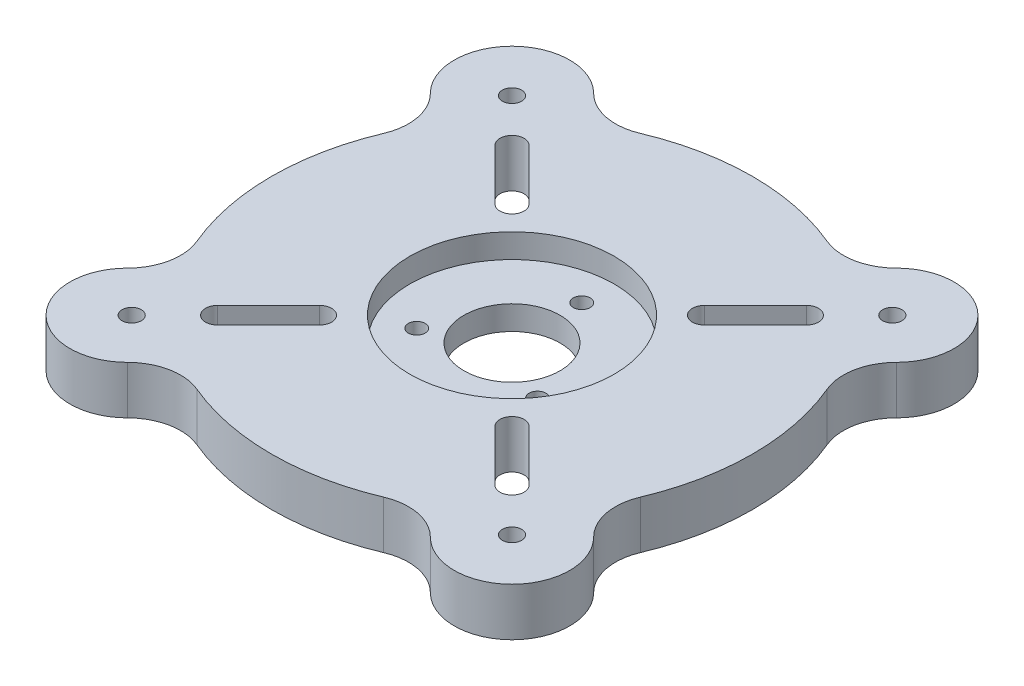
SolidWorks part; units mm, degrees
material "Cast Alloy Steel"
ref_plane "Front Plane" through (0, 0, 0) normal (0, 0, 1) x (1, 0, 0)
ref_plane "Top Plane" through (0, 0, 0) normal (0, 1, 0) x (1, 0, 0)
ref_plane "Right Plane" through (0, 0, 0) normal (1, 0, 0) x (0, 0, -1)
sketch "Sketch1" plane through (0, 0, 0) normal (0, 1, 0) x (1, 0, 0)
  line L0 (-39.9515, -39.9515) -> (39.9515, 39.9515) construction
  line L1 (-48.4368, -31.4663) -> (31.4663, 48.4368) construction
  line L2 (-31.4663, -48.4368) -> (48.4368, 31.4663) construction
  line L3 (0, 0) -> (0, 50) construction
  line L4 (39.9515, -39.9515) -> (-39.9515, 39.9515) construction
  line L5 (48.4368, -31.4663) -> (-31.4663, 48.4368) construction
  line L6 (31.4663, -48.4368) -> (-48.4368, 31.4663) construction
  line L7 (20, 20) -> (30.6066, 30.6066) construction
  line L8 (18.2322, 21.7678) -> (28.8388, 32.3744)
  line L9 (21.7678, 18.2322) -> (32.3744, 28.8388)
  line L10 (20, -20) -> (30.6066, -30.6066) construction
  line L11 (21.7678, -18.2322) -> (32.3744, -28.8388)
  line L12 (18.2322, -21.7678) -> (28.8388, -32.3744)
  line L13 (-20, -20) -> (-30.6066, -30.6066) construction
  line L14 (-18.2322, -21.7678) -> (-28.8388, -32.3744)
  line L15 (-21.7678, -18.2322) -> (-32.3744, -28.8388)
  line L16 (-20, 20) -> (-30.6066, 30.6066) construction
  line L17 (-21.7678, 18.2322) -> (-32.3744, 28.8388)
  line L18 (-18.2322, 21.7678) -> (-28.8388, 32.3744)
  circle A0 centre (0, 0) radius 50
  arc A1 (-48.4368, -31.4663) -> (-31.4663, -48.4368) centre (-39.9515, -39.9515) ccw construction
  arc A2 (48.4368, 31.4663) -> (31.4663, 48.4368) centre (39.9515, 39.9515) ccw construction
  arc A3 (48.4368, -31.4663) -> (31.4663, -48.4368) centre (39.9515, -39.9515) cw construction
  arc A4 (-48.4368, 31.4663) -> (-31.4663, 48.4368) centre (-39.9515, 39.9515) cw construction
  arc A5 (31.4663, 48.4368) -> (19.4135, 46.0773) centre (23.6858, 56.2173) cw
  arc A6 (48.4368, 31.4663) -> (46.0773, 19.4135) centre (56.2173, 23.6858) ccw
  arc A7 (18.2322, 21.7678) -> (21.7678, 18.2322) centre (20, 20) ccw
  arc A8 (32.3744, 28.8388) -> (28.8388, 32.3744) centre (30.6066, 30.6066) ccw
  circle A9 centre (39.5312, 39.5312) radius 2
  arc A10 (31.4663, 48.4368) -> (48.4368, 31.4663) centre (39.9515, 39.9515) cw
  arc A11 (48.4368, -31.4663) -> (31.4663, -48.4368) centre (39.9515, -39.9515) cw
  arc A12 (48.4368, -31.4663) -> (46.0773, -19.4135) centre (56.2173, -23.6858) cw
  arc A13 (31.4663, -48.4368) -> (19.4135, -46.0773) centre (23.6858, -56.2173) ccw
  circle A14 centre (39.5312, -39.5312) radius 2
  circle A15 centre (0, 0) radius 50
  arc A16 (21.7678, -18.2322) -> (18.2322, -21.7678) centre (20, -20) ccw
  arc A17 (28.8388, -32.3744) -> (32.3744, -28.8388) centre (30.6066, -30.6066) ccw
  arc A18 (-31.4663, -48.4368) -> (-48.4368, -31.4663) centre (-39.9515, -39.9515) cw
  arc A19 (-31.4663, -48.4368) -> (-19.4135, -46.0773) centre (-23.6858, -56.2173) cw
  arc A20 (-48.4368, -31.4663) -> (-46.0773, -19.4135) centre (-56.2173, -23.6858) ccw
  circle A21 centre (-39.5312, -39.5312) radius 2
  circle A22 centre (0, 0) radius 50
  arc A23 (-18.2322, -21.7678) -> (-21.7678, -18.2322) centre (-20, -20) ccw
  arc A24 (-32.3744, -28.8388) -> (-28.8388, -32.3744) centre (-30.6066, -30.6066) ccw
  arc A25 (-48.4368, 31.4663) -> (-31.4663, 48.4368) centre (-39.9515, 39.9515) cw
  arc A26 (-48.4368, 31.4663) -> (-46.0773, 19.4135) centre (-56.2173, 23.6858) cw
  arc A27 (-31.4663, 48.4368) -> (-19.4135, 46.0773) centre (-23.6858, 56.2173) ccw
  circle A28 centre (-39.5312, 39.5312) radius 2
  circle A29 centre (0, 0) radius 50
  arc A30 (-21.7678, 18.2322) -> (-18.2322, 21.7678) centre (-20, 20) ccw
  arc A31 (-28.8388, 32.3744) -> (-32.3744, 28.8388) centre (-30.6066, 30.6066) ccw
  point P5 (0, 0)
  point P13 (0, 0)
  point P24 (25.3033, 25.3033)
  point P45 (25.3033, -25.3033)
  point P63 (-25.3033, -25.3033)
  point P81 (-25.3033, 25.3033)
  point P90 (0, 0)
  dimension "D1" = 100
  dimension "D2" = 12
  dimension "D5" = 2.5
  dimension "D8" = 4
  dimension "D10" = 39.5312
  dimension "D3" = 113
  dimension "D4" = 45
  dimension "D6" = 15
  dimension "D7" = 20
  dimension "D9" = 4
extrude "Boss-Extrude1" add sketch "Sketch1" along normal blind 10 contours A20 A18 A19 A15 A21 | A0 A22 A15 A31 L18 A30 L17 A24 L15 A23 L14 A17 L12 A16 L11 A8 L9 A7 L8 | A13 A11 A12 A0 A14 | A10 A5 A0 A6 A9 | A27 A25 A26 A22 A28 region at (0, 0, 0) region at (35.6807, 0, -35.6807) region at (44.9674, 0, 25.8881) region at (-35.6807, 0, -35.6807) region at (-25.8881, 0, 44.9674)
sketch "Sketch2" plane through (0, 10, 0) normal (0, 1, 0) x (1, 0, 0)
  circle A0 centre (0, 0) radius 21.25
  circle A1 centre (0, 14.5) radius 1.75
  circle A2 centre (12.5574, -7.25) radius 1.75
  circle A3 centre (-12.5574, -7.25) radius 1.75
  circle A4 centre (0, 0) radius 10
  point P11 (0, 0)
  dimension "D1" = 42.5
  dimension "D2" = 3.5
  dimension "D7" = 20
  dimension "D3" = 14.5
  dimension "D4" = 14.5
  dimension "D5" = 14.5
  dimension "D6" = 3
extrude "Cut-Extrude5" cut sketch "Sketch2" against normal blind 5 contours A0 A3 A2 A1 | A3 | A1 | A2 region at (-20.649, 10, 0) region at (0, 10, -14.5) region at (12.5574, 10, 7.25) region at (-12.5574, 10, 7.25)
extrude "Cut-Extrude6" cut sketch "Sketch2<5>" against normal through all contours A4 | A3 | A1 | A2 region at (0, 10, 0)
sketch "Sketch2<5>" plane through (0, 10, 0) normal (0, 1, 0) x (1, 0, 0) same geometry as "Sketch2"
